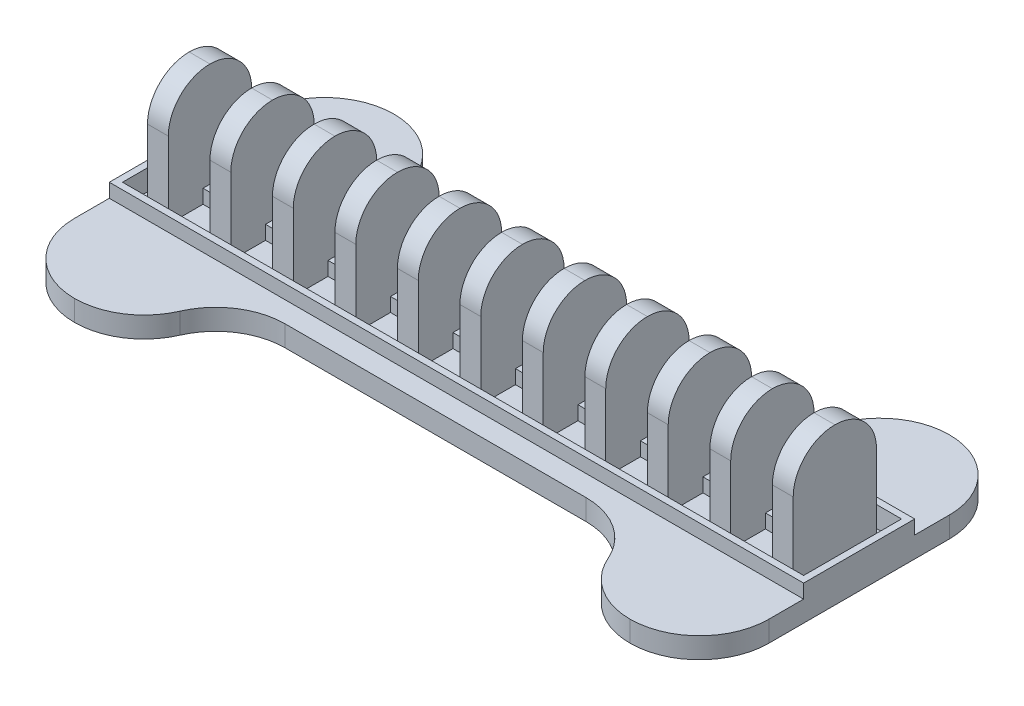
SolidWorks part; units mm, degrees
ref_plane "Front Plane" through (0, 0, 0) normal (0, 0, 1) x (1, 0, 0)
ref_plane "Top Plane" through (0, 0, 0) normal (0, 1, 0) x (1, 0, 0)
ref_plane "Right Plane" through (0, 0, 0) normal (1, 0, 0) x (0, 0, -1)
sketch "Sketch1" plane through (0, 0, 0) normal (0, 1, 0) x (1, 0, 0)
  line L1 (0, 0) -> (100, 0)
  line L2 (0, 0) -> (0, 16)
  line L3 (0, 16) -> (100, 16)
  line L4 (100, 0) -> (100, 16)
  dimension "D1" = 16
  dimension "D2" = 100
extrude "Boss-Extrude1" add sketch "Sketch1" along normal blind 3
sketch "Sketch2" plane through (0, 3, 0) normal (0, 1, 0) x (1, 0, 0)
  line L0 (0, 16) -> (0, 0) construction
  line L1 (1, 1) -> (99, 1)
  line L2 (1, 1) -> (1, 15)
  line L3 (1, 15) -> (99, 15)
  line L4 (99, 1) -> (99, 15)
  line L5 (100, 16) -> (0, 16) construction
  line L6 (0, 0) -> (100, 0) construction
  line L7 (100, 0) -> (100, 16) construction
  dimension "D1" = 1
  dimension "D2" = 1
  dimension "D3" = 1
  dimension "D4" = 1
extrude "Cut-Extrude1" cut sketch "Sketch2" against normal blind 1
sketch "Sketch5" plane through (0, 0, 0) normal (0, 0, 1) x (1, 0, 0)
  line L0 (0, 0) -> (100, 0) construction
  line L1 (0, 3) -> (20, 3)
  line L2 (0, 3) -> (0, 0)
  line L3 (0, 0) -> (20, 0)
  line L4 (20, 3) -> (20, 0)
  line L6 (100, 3) -> (80, 3)
  line L7 (100, 3) -> (100, 0)
  line L8 (100, 0) -> (80, 0)
  line L9 (80, 3) -> (80, 0)
  dimension "D1" = 20
  dimension "D2" = 20
extrude "Boss-Extrude4" add sketch "Sketch5" along normal blind 15
sketch "Sketch6" plane through (0, 0, -16) normal (0, 0, -1) x (-1, 0, 0)
  line L0 (-100, 0) -> (0, 0) construction
  line L1 (-100, 3) -> (-80, 3)
  line L2 (-100, 3) -> (-100, 0)
  line L3 (-100, 0) -> (-80, 0)
  line L4 (-80, 3) -> (-80, 0)
  line L6 (0, 3) -> (-20, 3)
  line L7 (0, 3) -> (0, 0)
  line L8 (0, 0) -> (-20, 0)
  line L9 (-20, 3) -> (-20, 0)
  dimension "D1" = 20
  dimension "D2" = 20
extrude "Boss-Extrude5" add sketch "Sketch6" along normal blind 15
fillet "Fillet18" radius 10 8 edges at (20, 1.5, 15) (0, 1.5, 15) (80, 1.5, 15) (100, 1.5, 15) (0, 1.5, -31) (20, 1.5, -31) (80, 1.5, -31) (100, 1.5, -31)
sketch "Sketch7" plane through (0, 2, 0) normal (0, 1, 0) x (1, 0, 0)
  line L0 (99, 1) -> (99, 15) construction
  line L1 (96.5, 2) -> (93.5, 2)
  line L2 (96.5, 2) -> (96.5, 14)
  line L3 (96.5, 14) -> (93.5, 14)
  line L4 (93.5, 2) -> (93.5, 14)
  line L5 (1, 1) -> (99, 1) construction
  line L6 (87.5, 2) -> (87.5, 14)
  line L7 (87.5, 2) -> (84.5, 2)
  line L8 (84.5, 2) -> (84.5, 14)
  line L9 (87.5, 14) -> (84.5, 14)
  line L10 (78.5, 2) -> (78.5, 14)
  line L11 (78.5, 2) -> (75.5, 2)
  line L12 (75.5, 2) -> (75.5, 14)
  line L13 (78.5, 14) -> (75.5, 14)
  line L14 (69.5, 2) -> (69.5, 14)
  line L15 (69.5, 2) -> (66.5, 2)
  line L16 (66.5, 2) -> (66.5, 14)
  line L17 (69.5, 14) -> (66.5, 14)
  line L18 (60.5, 2) -> (60.5, 14)
  line L19 (60.5, 2) -> (57.5, 2)
  line L20 (57.5, 2) -> (57.5, 14)
  line L21 (60.5, 14) -> (57.5, 14)
  line L22 (51.5, 2) -> (51.5, 14)
  line L23 (51.5, 2) -> (48.5, 2)
  line L24 (48.5, 2) -> (48.5, 14)
  line L25 (51.5, 14) -> (48.5, 14)
  line L26 (42.5, 2) -> (42.5, 14)
  line L27 (42.5, 2) -> (39.5, 2)
  line L28 (39.5, 2) -> (39.5, 14)
  line L29 (42.5, 14) -> (39.5, 14)
  line L30 (33.5, 2) -> (33.5, 14)
  line L31 (33.5, 2) -> (30.5, 2)
  line L32 (30.5, 2) -> (30.5, 14)
  line L33 (33.5, 14) -> (30.5, 14)
  line L34 (24.5, 2) -> (24.5, 14)
  line L35 (24.5, 2) -> (21.5, 2)
  line L36 (21.5, 2) -> (21.5, 14)
  line L37 (24.5, 14) -> (21.5, 14)
  line L38 (15.5, 2) -> (15.5, 14)
  line L39 (15.5, 2) -> (12.5, 2)
  line L40 (12.5, 2) -> (12.5, 14)
  line L41 (15.5, 14) -> (12.5, 14)
  line L42 (6.5, 2) -> (6.5, 14)
  line L43 (6.5, 2) -> (3.5, 2)
  line L44 (3.5, 2) -> (3.5, 14)
  line L45 (6.5, 14) -> (3.5, 14)
  line L46 (96.5, 2) -> (87.5, 2) construction
  dimension "D1" = 12
  dimension "D2" = 3
  dimension "D3" = 2.5
  dimension "D4" = 1
  dimension "D6" = 9
  dimension "D5" = 11
extrude "Boss-Extrude6" add sketch "Sketch7" along normal blind 17
sketch "Sketch8" plane through (0, 2, 0) normal (0, 1, 0) x (1, 0, 0)
  line L0 (93.5, 14) -> (93.5, 2) construction
  line L1 (93.5, 7) -> (87.5, 7)
  line L2 (93.5, 7) -> (93.5, 9)
  line L3 (93.5, 9) -> (87.5, 9)
  line L4 (87.5, 7) -> (87.5, 9)
  line L5 (87.5, 2) -> (87.5, 14) construction
  line L6 (99, 15) -> (1, 15) construction
  line L8 (84.5, 7) -> (84.5, 9)
  line L9 (84.5, 7) -> (78.5, 7)
  line L10 (78.5, 7) -> (78.5, 9)
  line L11 (84.5, 9) -> (78.5, 9)
  line L12 (75.5, 7) -> (75.5, 9)
  line L13 (75.5, 7) -> (69.5, 7)
  line L14 (69.5, 7) -> (69.5, 9)
  line L15 (75.5, 9) -> (69.5, 9)
  line L16 (66.5, 7) -> (66.5, 9)
  line L17 (66.5, 7) -> (60.5, 7)
  line L18 (60.5, 7) -> (60.5, 9)
  line L19 (66.5, 9) -> (60.5, 9)
  line L20 (57.5, 7) -> (57.5, 9)
  line L21 (57.5, 7) -> (51.5, 7)
  line L22 (51.5, 7) -> (51.5, 9)
  line L23 (57.5, 9) -> (51.5, 9)
  line L24 (48.5, 7) -> (48.5, 9)
  line L25 (48.5, 7) -> (42.5, 7)
  line L26 (42.5, 7) -> (42.5, 9)
  line L27 (48.5, 9) -> (42.5, 9)
  line L28 (39.5, 7) -> (39.5, 9)
  line L29 (39.5, 7) -> (33.5, 7)
  line L30 (33.5, 7) -> (33.5, 9)
  line L31 (39.5, 9) -> (33.5, 9)
  line L32 (30.5, 7) -> (30.5, 9)
  line L33 (30.5, 7) -> (24.5, 7)
  line L34 (24.5, 7) -> (24.5, 9)
  line L35 (30.5, 9) -> (24.5, 9)
  line L36 (21.5, 7) -> (21.5, 9)
  line L37 (21.5, 7) -> (15.5, 7)
  line L38 (15.5, 7) -> (15.5, 9)
  line L39 (21.5, 9) -> (15.5, 9)
  line L40 (12.5, 7) -> (12.5, 9)
  line L41 (12.5, 7) -> (6.5, 7)
  line L42 (6.5, 7) -> (6.5, 9)
  line L43 (12.5, 9) -> (6.5, 9)
  line L44 (93.5, 7) -> (84.5, 7) construction
  dimension "D1" = 2
  dimension "D2" = 6
  dimension "D3" = 10
  dimension "D4" = 9
extrude "Boss-Extrude7" add sketch "Sketch8" along normal blind 2
fillet "Fillet19" radius 6 22 edges at (95, 19, -2) (95, 19, -14) (86, 19, -2) (86, 19, -14) (77, 19, -2) (77, 19, -14) (68, 19, -2) (68, 19, -14) (59, 19, -2) (59, 19, -14) (50, 19, -2) (50, 19, -14) (41, 19, -2) (41, 19, -14) (32, 19, -2) (32, 19, -14) (23, 19, -14) (23, 19, -2) (14, 19, -2) (14, 19, -14) (5, 19, -2) (5, 19, -14)
sketch "Sketch10" plane through (0, 0, -16) normal (0, 0, -1) x (-1, 0, 0)
  line L1 (-80, 3) -> (-20, 3)
  line L2 (-80, 3) -> (-80, 0)
  line L3 (-80, 0) -> (-20, 0)
  line L4 (-20, 3) -> (-20, 0)
extrude "Boss-Extrude8" add sketch "Sketch10" along normal blind 3
sketch "Sketch11" plane through (0, 0, 0) normal (0, 0, 1) x (1, 0, 0)
  line L1 (20, 3) -> (80, 3)
  line L2 (20, 3) -> (20, 0)
  line L3 (20, 0) -> (80, 0)
  line L4 (80, 3) -> (80, 0)
extrude "Boss-Extrude9" add sketch "Sketch11" along normal blind 3
sketch "Sketch12" plane through (0, 3, 0) normal (0, 1, 0) x (1, 0, 0)
  line L0 (100, -5) -> (100, 21) construction
  line L1 (100, 14.9979) -> (99.05, 14.9979)
  line L2 (100, 14.9979) -> (100, 0.9979)
  line L3 (100, 0.9979) -> (99.05, 0.9979)
  line L4 (99.05, 14.9979) -> (99.05, 0.9979)
  line L5 (0, 21) -> (0, -5) construction
  line L6 (0, 14.9979) -> (0.95, 14.9979)
  line L7 (0, 14.9979) -> (0, 0.9979)
  line L8 (0, 0.9979) -> (0.95, 0.9979)
  line L9 (0.95, 14.9979) -> (0.95, 0.9979)
  dimension "D1" = 0.95
  dimension "D2" = 14
  dimension "D3" = 0.95
  dimension "D4" = 14
extrude "Boss-Extrude10" add sketch "Sketch12" along normal blind 3
sketch "Sketch13" plane through (0, 3, 0) normal (0, 1, 0) x (1, 0, 0)
  line L0 (0, 21) -> (0, 14.9979) construction
  line L1 (0, 15.05) -> (100, 15.05)
  line L2 (0, 15.05) -> (0, 16)
  line L3 (0, 16) -> (100, 16)
  line L4 (100, 15.05) -> (100, 16)
  line L5 (100, 14.9979) -> (100, 21) construction
  line L6 (100, -5) -> (100, 0.9979) construction
  line L7 (0, 0) -> (100, 0)
  line L8 (0, 0) -> (0, 0.95)
  line L9 (0, 0.95) -> (100, 0.95)
  line L10 (100, 0) -> (100, 0.95)
  line L11 (99, 15) -> (1, 15) construction
  line L13 (1, 1) -> (99, 1) construction
  dimension "D1" = 0.95
  dimension "D2" = 0.05
  dimension "D3" = 0.05
extrude "Boss-Extrude11" add sketch "Sketch13" along normal blind 3
sketch "Sketch14" plane through (0, 3, 0) normal (0, 1, 0) x (1, 0, 0)
  line L0 (0.95, 14.9979) -> (0, 14.9979) construction
  line L1 (0, 15.05) -> (0.95, 15.05)
  line L2 (0, 15.05) -> (0, 14.9979)
  line L3 (0, 14.9979) -> (0.95, 14.9979)
  line L4 (0.95, 15.05) -> (0.95, 14.9979)
  line L5 (0.95, 14.9979) -> (0, 14.9979) construction
extrude "Boss-Extrude12" add sketch "Sketch14" along normal blind 3
sketch "Sketch15" plane through (0, 3, 0) normal (0, 1, 0) x (1, 0, 0)
  line L0 (100, 0.95) -> (0, 0.95) construction
  line L1 (0, 0.9979) -> (0.95, 0.9979)
  line L2 (0, 0.9979) -> (0, 0.95)
  line L3 (0, 0.95) -> (0.95, 0.95)
  line L4 (0.95, 0.9979) -> (0.95, 0.95)
  line L6 (100, 0.9979) -> (99.0503, 0.9979)
  line L7 (100, 0.9979) -> (100, 0.95)
  line L8 (100, 0.95) -> (99.0503, 0.95)
  line L9 (99.0503, 0.9979) -> (99.0503, 0.95)
  line L10 (100, 15.05) -> (99.05, 15.05)
  line L11 (100, 15.05) -> (100, 14.9979)
  line L12 (100, 14.9979) -> (99.05, 14.9979)
  line L13 (99.05, 15.05) -> (99.05, 14.9979)
extrude "Boss-Extrude13" add sketch "Sketch15" along normal blind 3
ref_plane "Plane1" through (0, 6, 0) normal (0, 0, 1) x (1, 0, 0)
fillet "Fillet20" radius 10 4 edges at (20, 1.5, -19) (80, 1.5, -19) (80, 1.5, 3) (20, 1.5, 3)
sketch "Sketch17" plane through (0, 6, 0) normal (0, 1, 0) x (1, 0, 0)
  line L0 (0.95, 15.05) -> (0.95, 0.95)
  line L1 (0.95, 15.05) -> (99.05, 15.05)
  line L2 (0.95, 0.95) -> (99.05, 0.95)
  line L3 (99.05, 15.05) -> (99.05, 0.95)
  line L4 (99.05, 15.05) -> (99.05, 0.9979) construction
  line L5 (1.45, 14.55) -> (1.45, 1.45)
  line L6 (1.45, 1.45) -> (98.55, 1.45)
  line L7 (98.55, 14.55) -> (98.55, 1.45)
  line L8 (1.45, 14.55) -> (98.55, 14.55)
  dimension "D1" = 0.5
extrude "Cut-Extrude2" cut sketch "Sketch17" against normal blind 4
sketch "Sketch18" plane through (0, 6, 0) normal (0, 1, 0) x (1, 0, 0)
  line L0 (100, 16) -> (0, 16)
  line L1 (100, 16) -> (100, -0.05)
  line L2 (0, 16) -> (0, -0.05)
  line L3 (100, -0.05) -> (0, -0.05)
  line L4 (99, 15) -> (1, 15)
  line L5 (1, 15) -> (1, 0.95)
  line L6 (99, 0.95) -> (1, 0.95)
  line L7 (99, 15) -> (99, 0.95)
  line L8 (99.0503, 0.95) -> (0.95, 0.95) construction
  dimension "D1" = 1
extrude "Cut-Extrude3" cut sketch "Sketch18" against normal blind 2
sketch "Sketch19" plane through (0, 4, 0) normal (0, 1, 0) x (1, 0, 0)
  line L0 (99.05, 15.05) -> (99.05, 0.95)
  line L1 (100, 16) -> (0, 16)
  line L2 (100, 16) -> (100, 0)
  line L3 (100, 0) -> (0, 0)
  line L4 (0, 16) -> (0, 0)
  line L5 (99.05, 0.95) -> (0.95, 0.95)
  line L6 (0.95, 15.05) -> (0.95, 0.95)
  line L7 (99.05, 15.05) -> (0.95, 15.05)
  dimension "D1" = 0.95
extrude "Boss-Extrude14" add sketch "Sketch19" along normal blind 1
